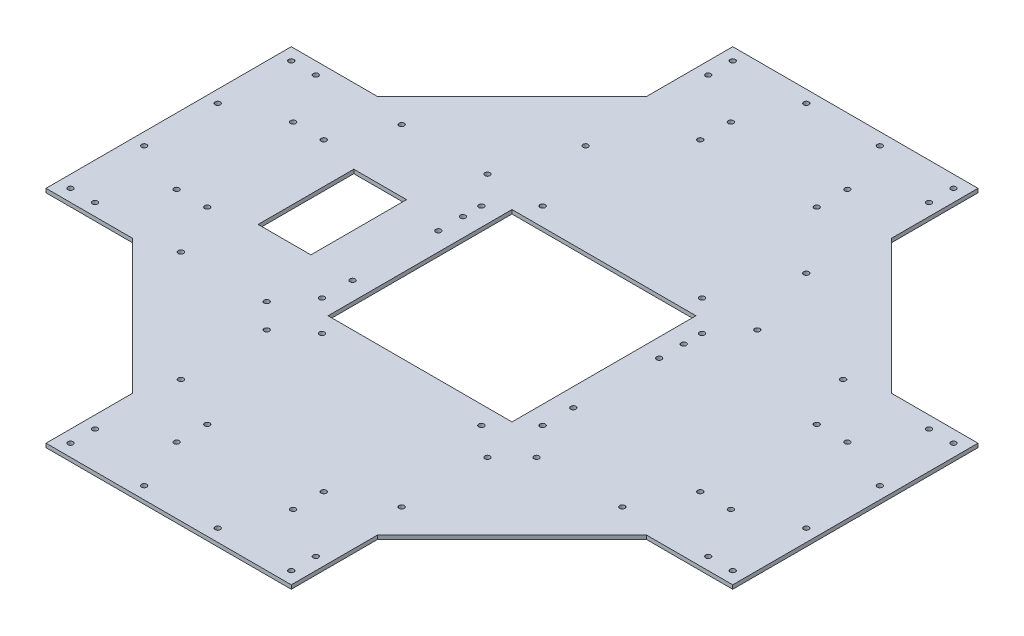
SolidWorks part; units mm, degrees
ref_plane "Front Plane" through (0, 0, 0) normal (0, 0, 1) x (1, 0, 0)
ref_plane "Top Plane" through (0, 0, 0) normal (0, 1, 0) x (1, 0, 0)
ref_plane "Right Plane" through (0, 0, 0) normal (1, 0, 0) x (0, 0, -1)
sketch "Sketch1" plane through (0, 0, 0) normal (0, 1, 0) x (1, 0, 0)
  line L0 (0, -280) -> (100, -280)
  line L1 (100, -280) -> (100, -209.6016)
  line L2 (280, -100) -> (209.6016, -100)
  line L3 (0, 0) -> (0, -280) construction
  line L4 (280, 0) -> (280, -100)
  line L5 (-280, 280) -> (280, 280) construction
  line L6 (-280, 280) -> (-280, -280) construction
  line L7 (-280, -280) -> (280, -280) construction
  line L8 (280, 280) -> (280, -280) construction
  line L9 (-280, 280) -> (280, -280) construction
  line L10 (-280, -280) -> (280, 280) construction
  line L11 (100, -209.6016) -> (209.6016, -100)
  line L12 (-280, 0) -> (-280, -100)
  line L13 (-280, -100) -> (-209.6016, -100)
  line L14 (-209.6016, -100) -> (-100, -209.6016)
  line L15 (-100, -280) -> (-100, -209.6016)
  line L16 (0, -280) -> (-100, -280)
  line L17 (0, 280) -> (-100, 280)
  line L18 (-100, 280) -> (-100, 209.6016)
  line L19 (-100, 209.6016) -> (-209.6016, 100)
  line L20 (-280, 100) -> (-209.6016, 100)
  line L21 (-280, 0) -> (-280, 100)
  line L22 (280, 0) -> (280, 100)
  line L23 (280, 100) -> (209.6016, 100)
  line L24 (209.6016, 100) -> (100, 209.6016)
  line L25 (100, 280) -> (100, 209.6016)
  line L26 (0, 280) -> (100, 280)
  line L27 (111.5258, -219.2889) -> (219.2889, -111.5258) construction
  line L28 (219.2889, -111.5258) -> (247.5732, -139.8101) construction
  line L29 (247.5732, -139.8101) -> (139.8101, -247.5732) construction
  line L30 (139.8101, -247.5732) -> (111.5258, -219.2889) construction
  line L31 (-100, -270) -> (100, -270) construction
  line L32 (-90, -280) -> (-90, 280) construction
  line L37 (-70, -70) -> (70, 70) construction
  line L38 (-70, 70) -> (70, -70) construction
  line L39 (-100, -260) -> (100, -260) construction
  line L40 (-280, 40) -> (280, 40) construction
  line L41 (0, 280) -> (0, 0) construction
  line L42 (-280, -90) -> (280, -90) construction
  line L43 (-260, -100) -> (-260, 100) construction
  line L44 (0, 0) -> (-280, 0) construction
  arc A0 (100, -280) -> (280, -100) centre (100, -100) ccw construction
  circle A1 centre (-47.5, -201) radius 2.125
  circle A2 centre (-47.5, -226) radius 2.125
  circle A3 centre (47.5, -226) radius 2.125
  circle A4 centre (47.5, -201) radius 2.125
  circle A5 centre (-201, 47.5) radius 2.125
  circle A6 centre (-226, 47.5) radius 2.125
  circle A7 centre (-201, -47.5) radius 2.125
  circle A8 centre (-226, -47.5) radius 2.125
  circle A9 centre (47.5, 201) radius 2.125
  circle A10 centre (47.5, 226) radius 2.125
  circle A11 centre (-47.5, 201) radius 2.125
  circle A12 centre (-47.5, 226) radius 2.125
  circle A13 centre (201, -47.5) radius 2.125
  circle A14 centre (226, -47.5) radius 2.125
  circle A15 centre (201, 47.5) radius 2.125
  circle A16 centre (226, 47.5) radius 2.125
  circle A17 centre (-90, -270) radius 2.125
  circle A18 centre (-30, -270) radius 2.125
  circle A19 centre (30, -270) radius 2.125
  circle A20 centre (90, -270) radius 2.125
  circle A21 centre (-270, 90) radius 2.125
  circle A22 centre (-270, 30) radius 2.125
  circle A23 centre (-270, -30) radius 2.125
  circle A24 centre (-270, -90) radius 2.125
  circle A25 centre (90, 270) radius 2.125
  circle A26 centre (30, 270) radius 2.125
  circle A27 centre (-30, 270) radius 2.125
  circle A28 centre (-90, 270) radius 2.125
  circle A29 centre (270, -90) radius 2.125
  circle A30 centre (270, -30) radius 2.125
  circle A31 centre (270, 30) radius 2.125
  circle A32 centre (270, 90) radius 2.125
  circle A33 centre (-90, -250) radius 2.125
  circle A34 centre (-90, -180) radius 2.125
  circle A35 centre (-90, -110) radius 2.125
  circle A36 centre (-90, -40) radius 2.125
  circle A37 centre (-90, 30) radius 2.125
  circle A38 centre (-90, 50) radius 2.125
  circle A39 centre (-90, 100) radius 2.125 construction
  circle A40 centre (-90, 150) radius 2.125
  circle A41 centre (-90, 200) radius 2.125 construction
  circle A42 centre (-90, 250) radius 2.125
  circle A43 centre (90, -250) radius 2.125
  circle A44 centre (90, -180) radius 2.125
  circle A45 centre (90, -110) radius 2.125
  circle A46 centre (90, -40) radius 2.125
  circle A47 centre (90, 30) radius 2.125
  circle A48 centre (90, 50) radius 2.125
  circle A49 centre (90, 100) radius 2.125 construction
  circle A50 centre (90, 150) radius 2.125
  circle A51 centre (90, 200) radius 2.125 construction
  circle A52 centre (90, 250) radius 2.125
  circle A53 centre (-250, -90) radius 2.125
  circle A54 centre (-180, -90) radius 2.125
  circle A55 centre (-110, -90) radius 2.125
  circle A56 centre (-110, 90) radius 2.125
  circle A57 centre (-180, 90) radius 2.125
  circle A58 centre (-250, 90) radius 2.125
  circle A59 centre (110, -90) radius 2.125
  circle A60 centre (180, -90) radius 2.125
  circle A61 centre (250, -90) radius 2.125
  circle A62 centre (110, 90) radius 2.125
  circle A63 centre (180, 90) radius 2.125
  circle A64 centre (250, 90) radius 2.125
  point P33 (0, 0)
  point P68 (0, 0)
  point P107 (0, 0)
  dimension "D10" = 25
  dimension "4.25" = 4.25
  dimension "D11" = 4.25
  dimension "D16" = 4.25
  dimension "D24" = 4.25
  dimension "D28" = 4.25
  dimension "D32" = 4.25
  dimension "D1" = 560
  dimension "D2" = 90
  dimension "D3" = 280
  dimension "D4" = 4
  dimension "D5" = 100
  dimension "D6" = 155
  dimension "D7" = 152.4
  dimension "D8" = 15
  dimension "D9" = 40
  dimension "D12" = 47.5
  dimension "D13" = 54
  dimension "D15" = 10
  dimension "D17" = 10
  dimension "D18" = 76.2
  dimension "D23" = 10
  dimension "D25" = 10
  dimension "D26" = 300
  dimension "D29" = 10
  dimension "D31" = 20
  dimension "D33" = 10
  dimension "D21" = 4
  dimension "D27" = 5
  dimension "D30" = 5
  dimension "D34" = 3
  dimension "D14" = 4
  dimension "D22" = 4
extrude "Boss-Extrude1" add sketch "Sketch1" along normal blind 3.175 contours L26 L17 L18 L19 L20 L21 L12 L13 L14 L15 L16 L0 L1 L11 L2 L4 L22 L23 L24 L25 region at (0, 0, -0.0137)
sketch "Sketch2" plane through (0, 3.175, 0) normal (0, 1, 0) x (1, 0, 0)
  line L0 (-90, -280) -> (-90, 280) construction
  line L1 (-75, -75) -> (75, -75)
  line L2 (-75, -75) -> (-75, 75)
  line L3 (-75, 75) -> (75, 75)
  line L4 (75, -75) -> (75, 75)
  line L5 (-75, -75) -> (75, 75) construction
  line L6 (-75, 75) -> (75, -75) construction
  line L7 (-90, -280) -> (-90, 280) construction
  line L8 (-75, 0) -> (75, 0) construction
  line L9 (0, 75) -> (0, -75) construction
  line L10 (-110, 90) -> (110, 90) construction
  line L12 (-168, -39) -> (-125, -39)
  line L13 (-168, -39) -> (-168, 39)
  line L14 (-168, 39) -> (-125, 39)
  line L15 (-125, -39) -> (-125, 39)
  line L16 (-168, -39) -> (-125, 39) construction
  line L17 (-168, 39) -> (-125, -39) construction
  circle A1 centre (-90, 65) radius 2.125
  circle A2 centre (-90, -65) radius 2.125
  circle A3 centre (90, -65) radius 2.125
  circle A4 centre (90, 65) radius 2.125
  circle A5 centre (-65, 90) radius 2.125
  circle A6 centre (65, 90) radius 2.125
  circle A7 centre (65, -90) radius 2.125
  circle A8 centre (-65, -90) radius 2.125
  point P0 (0, 0)
  point P6 (-146.5, 0)
  point P37 (-164, 0)
  dimension "D3" = 4.25
  dimension "D5" = 4.25
  dimension "D1" = 150
  dimension "D2" = 150
  dimension "D4" = 10
  dimension "D6" = 10
  dimension "D7" = 43
  dimension "D8" = 78
  dimension "D9" = 125
  dimension "D10" = 0
extrude "Cut-Extrude1" cut sketch "Sketch2" against normal through all
